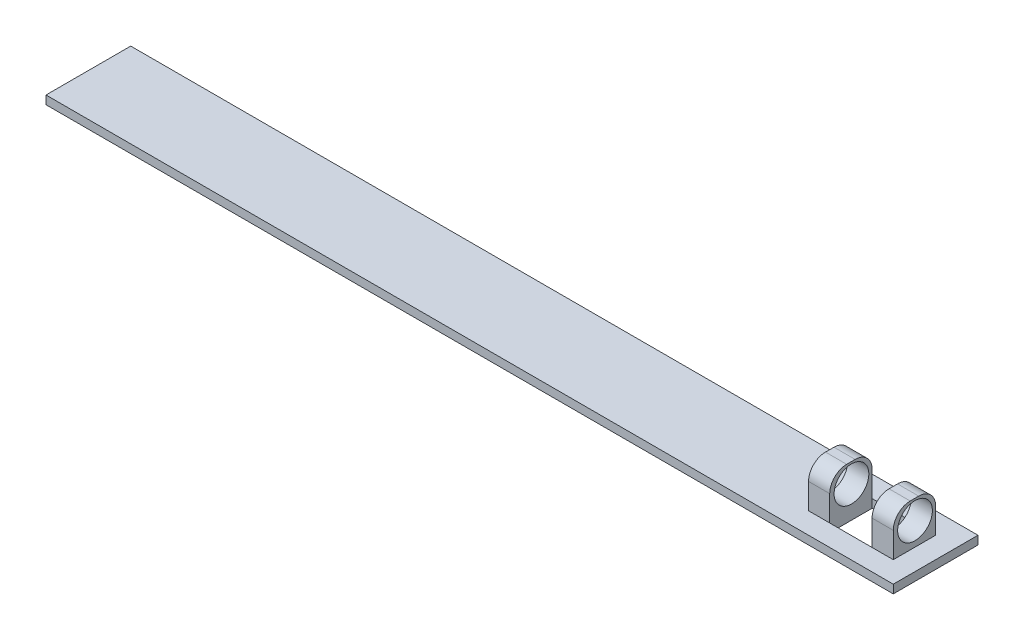
SolidWorks part; units mm, degrees
ref_plane "Front Plane" through (0, 0, 0) normal (0, 0, 1) x (1, 0, 0)
ref_plane "Top Plane" through (0, 0, 0) normal (0, 1, 0) x (1, 0, 0)
ref_plane "Right Plane" through (0, 0, 0) normal (1, 0, 0) x (0, 0, -1)
sketch "Sketch1" plane through (0, 0, 0) normal (0, 1, 0) x (1, 0, 0)
  line L1 (0, 0) -> (100, 0)
  line L2 (0, 0) -> (0, 10)
  line L3 (0, 10) -> (100, 10)
  line L4 (100, 0) -> (100, 10)
  line L5 (87.5, 2.5) -> (97.5, 2.5)
  line L6 (87.5, 2.5) -> (87.5, 7.5)
  line L7 (87.5, 7.5) -> (97.5, 7.5)
  line L8 (97.5, 2.5) -> (97.5, 7.5)
  line L9 (87.5, 2.5) -> (97.5, 7.5) construction
  line L10 (87.5, 7.5) -> (97.5, 2.5) construction
  line L11 (90, 2.5) -> (95, 2.5)
  line L12 (90, 2.5) -> (90, 7.5)
  line L13 (90, 7.5) -> (95, 7.5)
  line L14 (95, 2.5) -> (95, 7.5)
  line L15 (90, 2.5) -> (95, 7.5) construction
  line L16 (90, 7.5) -> (95, 2.5) construction
  point P5 (92.5, 5)
  point P10 (92.5, 5)
  dimension "D1" = 5
  dimension "D2" = 10
  dimension "D3" = 5
  dimension "D4" = 92.5
  dimension "D5" = 100
  dimension "D6" = 10
  dimension "D7" = 5
extrude "Boss-Extrude1" add sketch "Sketch1" along normal blind 5 contours L5 L12 L7 L6 | L14 L5 L8 L7 region at (88.75, 0, -5) region at (96.25, 0, -5)
extrude "Boss-Extrude2" add sketch "Sketch1<3>" against normal blind 1 separate body contours L1 L4 L3 L2 L8 L5 L6 L7 region at (47.7632, 0, -5)
sketch "Sketch1<3>" plane through (0, 0, 0) normal (0, 1, 0) x (1, 0, 0) same geometry as "Sketch1"
extrude "Boss-Extrude3" add sketch "Sketch1<4>" against normal blind 1 contours L5 L12 L7 L6 | L14 L5 L8 L7 region at (88.75, 0, -5) region at (96.25, 0, -5)
sketch "Sketch1<4>" plane through (0, 0, 0) normal (0, 1, 0) x (1, 0, 0) same geometry as "Sketch1"
sketch "Sketch2" plane through (97.5, 0, 0) normal (1, 0, 0) x (0, 0, -1)
  circle A0 centre (5.0651, 2.7101) radius 2.05
  dimension "D1" = 4.1
extrude "Cut-Extrude1" cut sketch "Sketch2" against normal through all
fillet "Fillet1" radius 2 4 edges at (96.25, 5, -7.5) (88.75, 5, -7.5) (96.25, 5, -2.5) (88.75, 5, -2.5)
